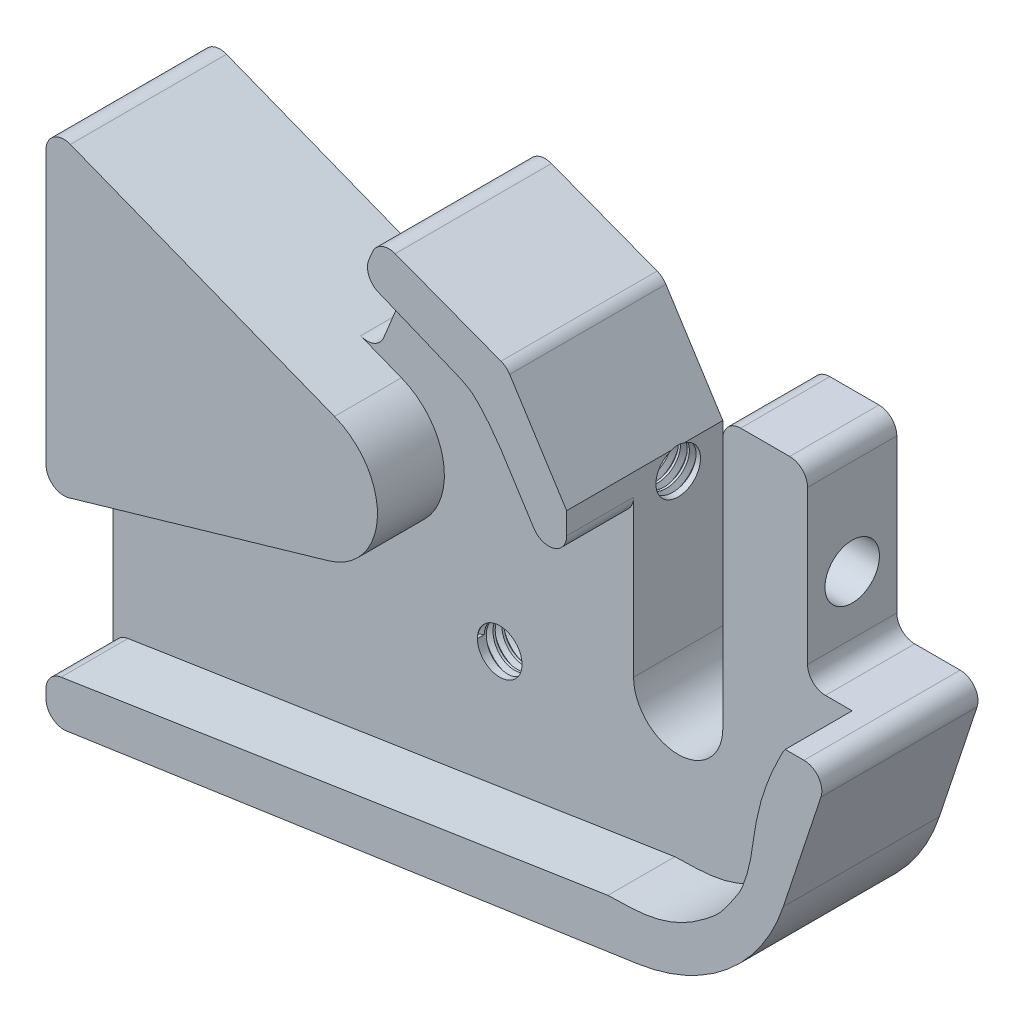
SolidWorks part; units mm, degrees
ref_plane "Front Plane" through (0, 0, 0) normal (0, 0, 1) x (1, 0, 0)
ref_plane "Top Plane" through (0, 0, 0) normal (0, 1, 0) x (1, 0, 0)
ref_plane "Right Plane" through (0, 0, 0) normal (1, 0, 0) x (0, 0, -1)
sketch "Sketch1" plane through (0, 0, 0) normal (0, 0, 1) x (1, 0, 0)
  line L0 (169.0465, 531.5792) -> (1384.9618, 942.3347) construction
  line L1 (17.1755, 0.269) -> (145.8355, -18.3486) construction
  line L2 (78.9683, 43.5936) -> (88.9683, 43.5936)
  line L3 (88.9683, 43.5936) -> (88.9683, 26.5936)
  line L4 (88.9683, 26.5936) -> (78.9683, 26.5936)
  line L5 (78.9683, 26.5936) -> (78.9683, 43.5936)
  line L6 (77.9414, 43.8024) -> (71.5407, 53.8656)
  line L7 (56.0381, 62.9033) -> (67.1668, 58.333)
  line L8 (88.9683, 43.5936) -> (88.9683, 61.7655)
  line L9 (88.9683, 61.7655) -> (98.4683, 61.7655)
  line L10 (77.9414, 43.8024) -> (78.9683, 42.1878)
  line L11 (20.6229, 24.1202) -> (53.1029, 33.5417)
  line L12 (23.9133, 59.0209) -> (55.1963, 46.7648)
  line L13 (56.0381, 62.9033) -> (50.2123, 48.7174)
  line L14 (70.5008, 62.7543) -> (72.231, 62.0968)
  line L15 (20.6229, 1.7639) -> (20.6229, 24.1202)
  line L16 (20.6229, 24.1202) -> (20.6229, 30.1202)
  line L17 (103.2745, 61.7655) -> (98.4683, 61.7655)
  line L18 (20.6229, 30.1202) -> (43.6301, 36.7939)
  line L19 (23.9133, 59.0209) -> (22.0894, 54.3655)
  line L20 (22.0894, 54.3655) -> (44.4958, 45.587)
  line L21 (78.9683, 43.5936) -> (78.9683, 49.4415)
  line L22 (57.9376, 67.5285) -> (70.5008, 62.7543)
  line L24 (40.0198, 35.7467) -> (40.0198, 47.3406)
  line L25 (40.0198, 47.3406) -> (40.0198, 52.7107)
  line L26 (56.0381, 62.9033) -> (57.9376, 67.5285)
  line L27 (103.4635, 40.5809) -> (108.336, 40.5809)
  line L28 (40.0198, 35.7467) -> (40.0198, 4.6135)
  line L29 (108.336, 40.5809) -> (99.307, 13.3233)
  line L30 (98.4683, 61.7655) -> (98.4683, 40.5809)
  line L31 (99.307, 13.3233) -> (20.6229, 1.7639)
  line L32 (83.9683, 43.5936) -> (83.9683, 46.6936)
  line L33 (20.6229, 6.4639) -> (20.6229, 6.7639)
  line L34 (20.6229, 6.7639) -> (83.6, 16.4882)
  line L35 (20.6229, 30.1202) -> (20.6229, 61.7655)
  line L36 (23.9133, 59.0209) -> (20.6229, 60.3101)
  line L37 (22.0894, 54.3655) -> (20.6229, 54.94)
  line L38 (73.7743, 50.3539) -> (77.9932, 53.0374) construction
  line L39 (77.9932, 53.0374) -> (71.1704, 63.7644)
  line L40 (77.9932, 53.0374) -> (78.9683, 51.5043)
  line L41 (78.9683, 51.5043) -> (78.9683, 49.4415)
  line L47 (98.4683, 40.5809) -> (103.4635, 40.5809)
  circle A0 centre (83.9683, 31.5936) radius 5
  circle A1 centre (83.9683, 38.5936) radius 5
  circle A5 centre (50.1903, 40.5872) radius 7.578
  circle A6 centre (103.2745, 54.3655) radius 4.4
  circle A7 centre (103.2745, 54.3655) radius 7.4
  circle A8 centre (83.9683, 31.5936) radius 20.3057
  spline S0 degree 3 poles (67.1668, 58.333) (67.5307, 58.1482) (68.2163, 57.8297) (69.7375, 56.3376) (70.7671, 54.998) (71.5407, 53.8656) knots 0 0 0 0 0.194176 0.353383 1 1 1 1
  spline S1 degree 3 poles (83.6, 16.4882) (85.4172, 16.5376) (87.878, 16.5192) (90.6726, 17.4205) (92.3949, 18.1773) (94.0998, 19.3373) (95.7619, 20.5842) (96.8381, 21.8934) (97.5722, 23.0215) (98.2993, 24.0127) (98.8168, 25.1807) (99.3382, 26.7948) (99.7545, 28.7331) (99.9792, 30.8782) (100.4112, 32.873) (100.8434, 34.6928) (101.4168, 36.2088) (101.8572, 37.4461) (102.3579, 38.4137) (102.8415, 39.4999) (103.165, 40.2018) (103.4635, 40.5809) knots 0 0 0 0 0.157684 0.206761 0.251698 0.319001 0.383658 0.429514 0.463788 0.499543 0.534878 0.573031 0.645405 0.704849 0.75836 0.820852 0.865423 0.897677 0.933689 0.958942 1 1 1 1
  spline S2 degree 3 poles (103.4635, 40.5809) (103.5281, 40.7021) (103.6539, 40.9177) (103.7777, 41.1891) (104.0324, 41.5752) (104.2845, 42.0418) (104.6133, 42.6639) (105.0506, 43.3284) (105.5376, 44.1633) (106.1189, 44.9679) (106.7473, 45.8247) (107.3304, 46.576) (107.8594, 47.2965) (108.3783, 47.8664) (108.8492, 48.4246) (109.2415, 48.9281) (109.5877, 49.4941) (110.1609, 50.7988) (110.3782, 52.0409) (110.5419, 52.9707) knots 0 0 0 0 0.032133 0.040138 0.080049 0.114202 0.15475 0.224504 0.279876 0.355143 0.430433 0.500504 0.552615 0.615873 0.660356 0.704255 0.748281 0.797656 1 1 1 1
  dimension "D7" = 5
  dimension "D5" = 8.8
  dimension "D6" = 14.8
  dimension "D1" = 130
  dimension "D2" = 10
  dimension "D3" = 17
  dimension "D4" = 9.5
  dimension "D8" = 5
  dimension "D9" = 5
  dimension "D10" = 5
extrude "Boss-Extrude1" add sketch "Sketch1" along normal blind 10 contours L34 S1 A8 L47 L30 L8 L3 L4 L5 L10 L6 | S0 L7 L13 L12 A5 L11 L28 L34 A8 L6 | A0 L5 L4 | A0 L4 L3 | A8 L30 A7 L9 L8 | A8 S1 L47 | L30 A7 | L15 L34 L28 L11 region at (78.4335, 40.3907, 0) region at (93.3717, 55.5464, 0) region at (87.8514, 27.7104, 0) region at (80.0851, 27.7104, 0) region at (56.6282, 32.8832, 0) region at (97.4134, 54.3655, 0) region at (102.785, 40.1666, 0) region at (30.5491, 17.6481, 0)
extrude "Boss-Extrude2" add sketch "Sketch1<3>" along normal blind 17.5 contours L7 S0 L6 A8 L41 L40 L39 L14 L22 L26 | L41 A8 L6 L10 L5 L21 | A5 | A5 L12 L25 L20 | A5 L20 L24 L18 | A5 L18 L28 L11 | A8 L34 L28 L31 | S1 L34 A8 | S1 A8 L29 L27 | L20 L25 L12 L19 | L37 L19 L36 L35 | L20 L37 L35 L18 L24 | L28 L18 L11 | L34 L15 L31 L28 region at (77.4058, 47.7092, 0) region at (68.0812, 59.4299, 0) region at (58.9314, 9.8932, 0) region at (78.1518, 15.2189, 0) region at (30.3677, 5.732, 0) region at (105.2761, 36.6233, 0) region at (43.4702, 33.1986, 0) region at (30.3213, 29.9334, 0) region at (43.8977, 48.9301, 0) region at (50.1903, 40.5872, 0) region at (41.5617, 41.668, 0) region at (29.1471, 42.0966, 0) region at (31.5024, 53.3147, 0) region at (21.8704, 57.4794, 0)
sketch "Sketch1<3>" plane through (0, 0, 0) normal (0, 0, 1) x (1, 0, 0) same geometry as "Sketch1"
fillet "Fillet1" radius 2 13 edges at (108.336, 40.5809, 8.75) (98.4683, 61.7655, 5) (88.9683, 61.7655, 5) (57.9376, 67.5285, 8.75) (56.0381, 62.9033, 13.75) (78.9683, 42.1878, 13.75) (20.6229, 1.7639, 8.75) (50.2123, 48.7174, 5) (98.4683, 40.5809, 5) (20.6229, 6.7639, 13.75) (72.231, 62.0968, 8.75) (20.6229, 24.1202, 13.75) (20.6229, 60.3101, 8.75)
sketch "Sketch4" plane through (88.9683, 0, 0) normal (-1, 0, 0) x (0, 0, 1)
  line L0 (5, 31.5936) -> (5, 49.0936)
  line L1 (10, 31.5936) -> (0, 31.5936) construction
  circle A0 centre (5, 49.0936) radius 3.05
  dimension "D1" = 17.5
extrude "Cut-Extrude2" cut sketch "Sketch4" against normal blind 30 contours A0 region at (88.9683, 46.9979, 7.0957)
hole_wizard "Tap Drill for M6x1.0 Tap3" positions "3DSketch7" profile "Sketch10" hole size "M6x1.0" standard "ANSI Metric"
sketch3d "3DSketch7"
  line L0 (98.4683, 49.0936, 5) -> (88.9683, 49.0936, 5) construction
  point P0 (88.9683, 49.0936, 5)
sketch "Sketch10" plane through (88.9683, 49.0936, 5) normal (0, 1, 0) x (0, 0, -1)
  line L0 (0, 0) -> (0, 31.5022)
  line L1 (0, 31.5022) -> (2.5, 30)
  line L2 (2.5, 30) -> (2.5, 0)
  line L5 (2.5, 0) -> (0, 0)
  line L10 (0, 31.5022) -> (-2.5, 30) construction
  line L11 (0, -6.35) -> (0, 107.95) construction
  dimension "Hole Dia." = 5
  dimension "Hole Depth" = 30
  dimension "Drill Angle" = 118
thread "Thread2" pitch 1 method cut profile "Thread Profile2" start angle 0, offset 0, length 20, pitch 1, diameter 5
ref_plane "Plane2" through (78.9683, 49.0936, 7.5) normal (0, -1, 0) x (0, 0, 1)
sketch "Thread Profile2" plane through (78.9683, 49.0936, 7.5) normal (0, -1, 0) x (0, 0, 1)
  line L0 (0, 0) -> (0, 1) construction
  line L1 (0, 0) -> (0.5413, 0.3125)
  line L2 (0.5413, 0.3125) -> (0.5413, 0.4375)
  line L3 (0.5413, 0.4375) -> (0, 0.75)
  line L4 (0.5413, 0.375) -> (0, 0.375) construction
  line L11 (0, 0) -> (0, 0.75)
  point P2 (0, 0)
  dimension "Pitch" = 1
  dimension "Profile_Angle" = 60
  dimension "Profile_Land" = 0.125
  dimension "Profile_Height" = 0.5413
sketch "Sketch14" plane through (0, 0, 10) normal (0, 0, 1) x (1, 0, 0)
  line L0 (83.9683, 26.5936) -> (63.9683, 26.5936)
  arc A0 (78.9683, 31.5936) -> (88.9683, 31.5936) centre (83.9683, 31.5936) ccw construction
hole_wizard "Tap Drill for M6x1.0 Tap4" positions "3DSketch11" profile "Sketch15" hole size "M6x1.0" standard "ANSI Metric"
sketch3d "3DSketch11"
  point P0 (63.9683, 26.5936, 10)
sketch "Sketch15" plane through (63.9683, 26.5936, 10) normal (1, 0, 0) x (0, -1, 0)
  line L0 (0, 0) -> (0, 31.5022)
  line L1 (0, 31.5022) -> (2.5, 30)
  line L2 (2.5, 30) -> (2.5, 0)
  line L5 (2.5, 0) -> (0, 0)
  line L10 (0, 31.5022) -> (-2.5, 30) construction
  line L11 (0, -6.35) -> (0, 107.95) construction
  dimension "Hole Dia." = 5
  dimension "Hole Depth" = 30
  dimension "Drill Angle" = 118
thread "Thread3" pitch 1 method cut profile "Thread Profile3" start angle 0, offset 0, length 20, pitch 1, diameter 5
ref_plane "Plane3" through (61.4683, 26.5936, 10) normal (0, -1, 0) x (-1, 0, 0)
sketch "Thread Profile3" plane through (61.4683, 26.5936, 10) normal (0, -1, 0) x (-1, 0, 0)
  line L0 (0, 0) -> (0, 1) construction
  line L1 (0, 0) -> (0.5413, 0.3125)
  line L2 (0.5413, 0.3125) -> (0.5413, 0.4375)
  line L3 (0.5413, 0.4375) -> (0, 0.75)
  line L4 (0.5413, 0.375) -> (0, 0.375) construction
  line L11 (0, 0) -> (0, 0.75)
  point P2 (0, 0)
  dimension "Pitch" = 1
  dimension "Profile_Angle" = 60
  dimension "Profile_Land" = 0.125
  dimension "Profile_Height" = 0.5413
